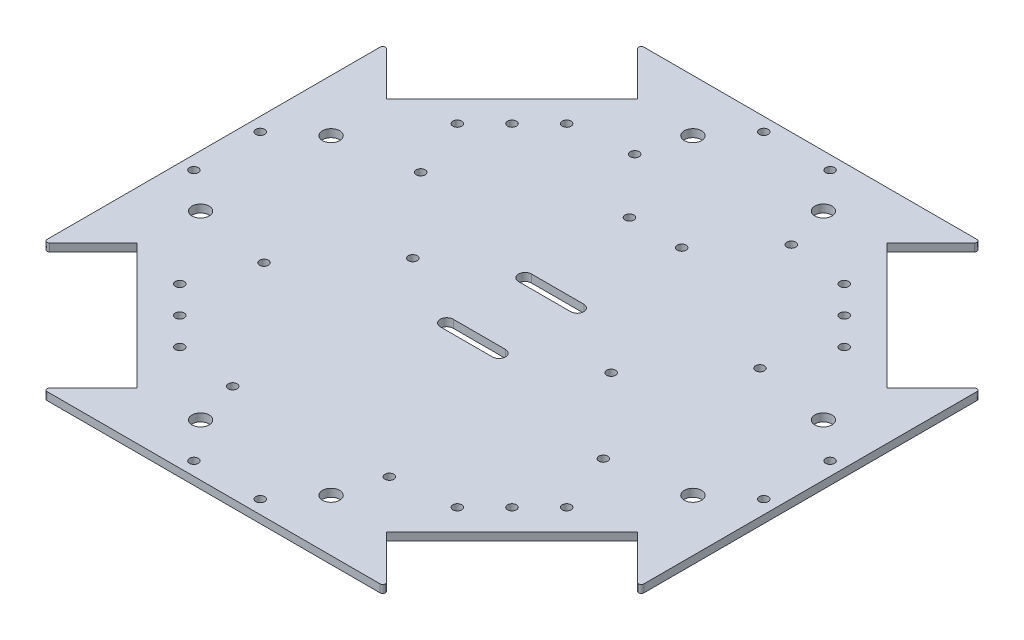
SolidWorks part; units mm, degrees
ref_plane "Front Plane" through (0, 0, 0) normal (0, 0, 1) x (1, 0, 0)
ref_plane "Top Plane" through (0, 0, 0) normal (0, 1, 0) x (1, 0, 0)
ref_plane "Right Plane" through (0, 0, 0) normal (1, 0, 0) x (0, 0, -1)
sketch "Sketch1" plane through (0, 0, 0) normal (0, 1, 0) x (1, 0, 0)
  line L1 (-114.3, 114.3) -> (114.3, 114.3)
  line L2 (-114.3, 114.3) -> (-114.3, -114.3)
  line L3 (-114.3, -114.3) -> (114.3, -114.3)
  line L4 (114.3, 114.3) -> (114.3, -114.3)
  line L5 (-114.3, 114.3) -> (114.3, -114.3) construction
  line L6 (-114.3, -114.3) -> (114.3, 114.3) construction
  point P0 (0, 0)
  dimension "D1" = 228.6
  dimension "D2" = 228.6
extrude "plate" add sketch "Sketch1" along normal blind 3
sketch "Sketch8" plane through (0, 3, 0) normal (0, 1, 0) x (1, 0, 0)
  line L0 (-114.3, 114.3) -> (114.3, -114.3) construction
  line L1 (114.3, 114.3) -> (-114.3, -114.3) construction
  line L2 (-50.6604, 177.9396) -> (177.9396, -50.6604) construction
  line L3 (0, 0) -> (63.6396, 63.6396) construction
  circle A0 centre (63.6396, 63.6396) radius 1.7
  circle A1 centre (74.1048, 53.1744) radius 1.7
  circle A2 centre (53.1744, 74.1048) radius 1.7
  circle A3 centre (63.6396, -63.6396) radius 1.7
  circle A4 centre (74.1048, -53.1744) radius 1.7
  circle A5 centre (53.1744, -74.1048) radius 1.7
  circle A6 centre (-63.6396, -63.6396) radius 1.7
  circle A7 centre (-53.1744, -74.1048) radius 1.7
  circle A8 centre (-74.1048, -53.1744) radius 1.7
  circle A9 centre (-63.6396, 63.6396) radius 1.7
  circle A10 centre (-74.1048, 53.1744) radius 1.7
  circle A11 centre (-53.1744, 74.1048) radius 1.7
  dimension "D2" = 3.4
  dimension "D3" = 3.4
  dimension "D4" = 3.4
  dimension "D5" = 14.8
  dimension "D6" = 14.8
  dimension "D8" = 90
  dimension "D9" = 90
  dimension "D1" = 90
  dimension "D7" = 4
extrude "motor-mount-holes" cut sketch "Sketch8" against normal blind 3
sketch "Sketch9" plane through (0, 3, 0) normal (0, 1, 0) x (1, 0, 0)
  line L0 (0, -114.3) -> (0, 114.3) construction
  line L1 (-38, 0) -> (38, 0) construction
  line L4 (114.3, 114.3) -> (-114.3, 114.3) construction
  line L5 (-114.3, -114.3) -> (114.3, -114.3) construction
  circle A0 centre (-38, 0) radius 1.7
  circle A1 centre (38, 0) radius 1.7
  point P2 (-2.4583, -4.5233)
  point P3 (0, 0)
  dimension "D3" = 3.4
  dimension "D2" = 38
extrude "connector-board-holes" cut sketch "Sketch9" against normal blind 3
sketch "Sketch11" plane through (0, 3, 0) normal (0, 1, 0) x (1, 0, 0)
  line L0 (-114.3, 0) -> (114.3, 0) construction
  line L1 (-114.3, 55) -> (114.3, 55) construction
  line L2 (0, -114.3) -> (0, 114.3) construction
  line L3 (27.5, -114.3) -> (27.5, 114.3) construction
  line L4 (-27.5, -114.3) -> (-27.5, 114.3) construction
  line L5 (-123.5172, 0) -> (114.3, 0) construction
  line L6 (-114.3, 114.3) -> (-114.3, -114.3) construction
  line L7 (114.3, -114.3) -> (114.3, 114.3) construction
  line L8 (0, -94.2235) -> (0, 114.3) construction
  line L9 (114.3, 114.3) -> (-114.3, 114.3) construction
  line L10 (-114.3, -114.3) -> (114.3, -114.3) construction
  line L11 (-123.5172, 55) -> (114.3, 55) construction
  line L12 (-27.5, -94.2235) -> (-27.5, 114.3) construction
  line L13 (27.5, -94.2235) -> (27.5, 114.3) construction
  circle A0 centre (-10, 55) radius 1.7
  circle A1 centre (10, 55) radius 1.7
  dimension "D4" = 3.4
  dimension "D5" = 3.4
  dimension "D6" = 10
  dimension "D7" = 20
  dimension "D1" = 55
  dimension "D2" = 27.5
  dimension "D3" = 27.5
extrude "motor-controller-holder-arduino-holes" cut sketch "Sketch11" against normal up to next
sketch "Sketch12" plane through (0, 3, 0) normal (0, 1, 0) x (1, 0, 0)
  line L0 (114.3, 0) -> (-114.3, 0) construction
  line L1 (114.3, -114.3) -> (114.3, 114.3) construction
  line L2 (-114.3, 114.3) -> (-114.3, -114.3) construction
  line L3 (-10, 15) -> (10, 15) construction
  line L4 (-10, 17.5) -> (10, 17.5)
  line L5 (-10, 12.5) -> (10, 12.5)
  line L6 (-10, -15) -> (10, -15) construction
  line L7 (-10, -12.5) -> (10, -12.5)
  line L8 (-10, -17.5) -> (10, -17.5)
  line L9 (0, 114.3) -> (0, -114.3) construction
  line L10 (114.3, 114.3) -> (-114.3, 114.3) construction
  line L11 (-114.3, -114.3) -> (114.3, -114.3) construction
  arc A0 (-10, 17.5) -> (-10, 12.5) centre (-10, 15) ccw
  arc A1 (10, 12.5) -> (10, 17.5) centre (10, 15) ccw
  arc A2 (-10, -12.5) -> (-10, -17.5) centre (-10, -15) ccw
  arc A3 (10, -17.5) -> (10, -12.5) centre (10, -15) ccw
  point P8 (0, 15)
  point P13 (0, -15)
  dimension "D5" = 2.5
  dimension "D6" = 2.5
  dimension "D1" = 15
  dimension "D2" = 15
  dimension "D3" = 20
  dimension "D4" = 20
extrude "cable-slots" cut sketch "Sketch12" against normal up to next
sketch "Sketch13" plane through (0, 3, 0) normal (0, 1, 0) x (1, 0, 0)
  line L0 (0, -114.3) -> (0, 114.3) construction
  line L1 (-114.3, -114.3) -> (114.3, -114.3) construction
  line L2 (114.3, 114.3) -> (-114.3, 114.3) construction
  line L3 (-114.3, 109.1438) -> (114.3, 109.1438) construction
  line L4 (-114.3, 114.3) -> (-114.3, -114.3) construction
  line L5 (114.3, -114.3) -> (114.3, 114.3) construction
  line L6 (0, 0) -> (12.7, 109.1438) construction
  circle A0 centre (-12.7, 109.1438) radius 1.7
  circle A1 centre (12.7, 109.1438) radius 1.7
  circle A8 centre (109.1438, 12.7) radius 1.7
  circle A9 centre (109.1438, -12.7) radius 1.7
  circle A10 centre (12.7, -109.1438) radius 1.7
  circle A11 centre (-12.7, -109.1438) radius 1.7
  circle A12 centre (-109.1438, -12.7) radius 1.7
  circle A13 centre (-109.1438, 12.7) radius 1.7
  dimension "D2" = 3.4
  dimension "D3" = 3.4
  dimension "D1" = 5.1562
  dimension "D4" = 12.7
  dimension "D5" = 12.7
  dimension "D7" = 109.8802
  dimension "D8" = 6.637
  dimension "D6" = 4
extrude "wall-bracket-holes" cut sketch "Sketch13" against normal up to next
sketch "Sketch14" plane through (0, 3, 0) normal (0, 1, 0) x (1, 0, 0)
  line L0 (-114.3, 0) -> (114.3, 0) construction
  line L1 (-114.3, 114.3) -> (-114.3, -114.3) construction
  line L2 (114.3, -114.3) -> (114.3, 114.3) construction
  line L4 (0, 114.3) -> (0, -114.3) construction
  line L5 (114.3, 114.3) -> (-114.3, 114.3) construction
  line L6 (-114.3, -114.3) -> (114.3, -114.3) construction
  line L7 (-65, 30) -> (-65, -30) construction
  circle A8 centre (-65, 30) radius 1.7
  circle A9 centre (-65, -30) radius 1.7
  circle A10 centre (65, -30) radius 1.7
  circle A11 centre (65, 30) radius 1.7
  point P26 (-65, 0)
  dimension "D6" = 3.4
  dimension "D7" = 30
  dimension "D8" = 65
extrude "battery-holder-holes" cut sketch "Sketch14" against normal up to next
sketch "Sketch15" plane through (0, 3, 0) normal (0, 1, 0) x (1, 0, 0)
  line L0 (114.3, 0) -> (-114.3, 0) construction
  line L1 (114.3, -114.3) -> (114.3, 114.3) construction
  line L2 (-114.3, 114.3) -> (-114.3, -114.3) construction
  line L3 (114.3, 114.3) -> (-114.3, 114.3) construction
  line L4 (-25, 94.3) -> (25, 94.3) construction
  line L5 (-25, -94.3) -> (25, -94.3) construction
  line L6 (-114.3, -114.3) -> (114.3, -114.3) construction
  line L8 (0, 94.3) -> (0, 114.3) construction
  circle A0 centre (-94.3, 25) radius 3.3
  circle A1 centre (-94.3, -25) radius 3.3
  circle A2 centre (94.3, 25) radius 3.3
  circle A3 centre (94.3, -25) radius 3.3
  circle A4 centre (25, 94.3) radius 3.3
  circle A5 centre (-25, 94.3) radius 3.3
  circle A6 centre (25, -94.3) radius 3.3
  circle A7 centre (-25, -94.3) radius 3.3
  point P25 (0, 0)
  dimension "D3" = 6.6
  dimension "D4" = 6.6
  dimension "D6" = 6.6
  dimension "D7" = 6.6
  dimension "D13" = 20
  dimension "D1" = 50
  dimension "D2" = 25
  dimension "D5" = 20
  dimension "D8" = 25
  dimension "D9" = 50
  dimension "D10" = 20
  dimension "D12" = 20
  dimension "D11" = 2
extrude "load-mount-holes" cut sketch "Sketch15" against normal up to next
sketch "Sketch10" plane through (0, 3, 0) normal (0, 1, 0) x (1, 0, 0)
  line L0 (0, 114.3) -> (0, -114.3) construction
  line L1 (114.3, 114.3) -> (-114.3, 114.3) construction
  line L2 (-114.3, -114.3) -> (114.3, -114.3) construction
  line L3 (-114.3, 0) -> (114.3, 0) construction
  line L4 (-114.3, 114.3) -> (-114.3, -114.3) construction
  line L5 (114.3, -114.3) -> (114.3, 114.3) construction
  line L6 (30, 77) -> (-30, 77) construction
  line L7 (-30, 77) -> (-30, -77) construction
  circle A5 centre (30, 77) radius 1.7
  circle A6 centre (30, -77) radius 1.7
  circle A7 centre (-30, -77) radius 1.7
  circle A8 centre (-30, 77) radius 1.7
  point P20 (0, 77)
  point P21 (-30, 0)
  dimension "D1" = 3.4
  dimension "D2" = 30
  dimension "D3" = 77
extrude "level2-standoff-holes" cut sketch "Sketch10" against normal up to next
sketch "Sketch2" plane through (0, 3, 0) normal (0, 1, 0) x (1, 0, 0)
  line L0 (-114.3, -114.3) -> (114.3, 114.3) construction
  line L1 (114.3, -114.3) -> (-114.3, 114.3) construction
  line L2 (-90.2584, -138.3416) -> (138.3416, 90.2584) construction
  line L3 (-138.3416, -90.2584) -> (90.2584, 138.3416) construction
  line L4 (186.142, -42.458) -> (-42.458, 186.142) construction
  line L5 (114.3, 114.3) -> (66.2167, 114.3)
  line L6 (114.3, 114.3) -> (-114.3, 114.3) construction
  line L7 (66.2167, 114.3) -> (47.8004, 95.8837)
  line L8 (47.8004, 95.8837) -> (95.8837, 47.8004)
  line L9 (95.8837, 47.8004) -> (114.3, 66.2167)
  line L10 (114.3, 66.2167) -> (114.3, 114.3)
  line L41 (66.2167, -114.3) -> (114.3, -114.3)
  line L42 (114.3, -114.3) -> (114.3, -66.2167)
  line L43 (114.3, -66.2167) -> (95.8837, -47.8004)
  line L44 (95.8837, -47.8004) -> (47.8004, -95.8837)
  line L45 (47.8004, -95.8837) -> (66.2167, -114.3)
  line L46 (-114.3, -66.2167) -> (-114.3, -114.3)
  line L47 (-114.3, -114.3) -> (-66.2167, -114.3)
  line L48 (-66.2167, -114.3) -> (-47.8004, -95.8837)
  line L49 (-47.8004, -95.8837) -> (-95.8837, -47.8004)
  line L50 (-95.8837, -47.8004) -> (-114.3, -66.2167)
  line L51 (-66.2167, 114.3) -> (-114.3, 114.3)
  line L52 (-114.3, 114.3) -> (-114.3, 66.2167)
  line L53 (-114.3, 66.2167) -> (-95.8837, 47.8004)
  line L54 (-95.8837, 47.8004) -> (-47.8004, 95.8837)
  line L55 (-47.8004, 95.8837) -> (-66.2167, 114.3)
  line L56 (0, 0) -> (95.8837, 47.8004) construction
  dimension "D5" = 107.138
  dimension "D6" = 18.503
  dimension "D1" = 34
  dimension "D2" = 34
  dimension "D3" = 101.6
  dimension "D4" = 4
extrude "wheel-slots" cut sketch "Sketch2" against normal blind 3
fillet "Fillet1" radius 1 8 edges at (66.2167, 1.5, -114.3) (114.3, 1.5, -66.2167) (114.3, 1.5, 66.2167) (-66.2167, 1.5, -114.3) (-114.3, 1.5, -66.2167) (-114.3, 1.5, 66.2167) (-66.2167, 1.5, 114.3) (66.2167, 1.5, 114.3)
